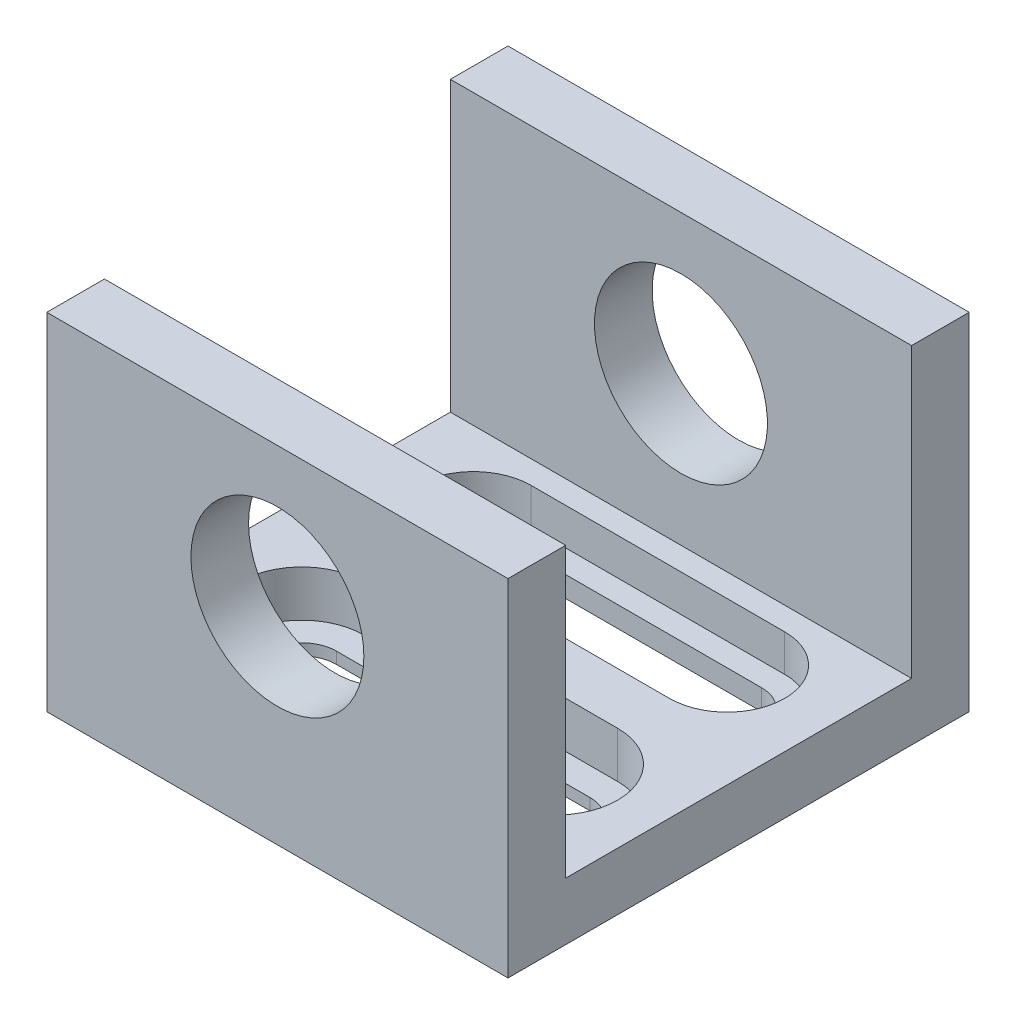
SolidWorks part; units mm, degrees
ref_plane "Front Plane" through (0, 0, 0) normal (0, 0, 1) x (1, 0, 0)
ref_plane "Top Plane" through (0, 0, 0) normal (0, 1, 0) x (1, 0, 0)
ref_plane "Right Plane" through (0, 0, 0) normal (1, 0, 0) x (0, 0, -1)
sketch "Sketch1" plane through (-35.1459, 0, 0) normal (1, 0, 0) x (0, 0, -1)
  line L1 (0, 0) -> (-19.05, 0)
  line L3 (0, 3.175) -> (-19.05, 3.175)
  line L5 (3.175, 19.05) -> (0, 19.05)
  line L6 (3.175, 19.05) -> (3.175, 0)
  line L7 (3.175, 0) -> (0, 0)
  line L8 (0, 19.05) -> (0, 3.175)
  line L13 (-19.05, 0) -> (-22.225, 0)
  line L14 (-19.05, 3.175) -> (-19.05, 19.05)
  line L15 (-19.05, 19.05) -> (-22.225, 19.05)
  line L16 (-22.225, 0) -> (-22.225, 19.05)
  dimension "D2" = 3.175
  dimension "D3" = 3.175
  dimension "D4" = 19.05
  dimension "D5" = 19.05
extrude "Boss-Extrude2" add sketch "Sketch1" along normal blind 25.4
sketch "Sketch3" plane through (0, 0, -3.175) normal (0, 0, -1) x (-1, 0, 0)
  line L0 (9.7459, 0) -> (35.1459, 0) construction
  line L2 (35.1459, 0) -> (35.1459, 19.05) construction
  circle A0 centre (22.4459, 11.3665) radius 4.7625
  dimension "D1" = 11.3665
  dimension "D2" = 12.7
extrude "Cut-Extrude1" cut sketch "Sketch3" against normal blind 36.576
sketch "Sketch4" plane through (0, 3.175, 0) normal (0, 1, 0) x (1, 0, 0)
  line L1 (-29.4309, -1.27) -> (-15.4609, -1.27)
  line L3 (-29.4309, -2.54) -> (-15.4609, -2.54)
  line L5 (-29.4309, -6.35) -> (-15.4609, -6.35)
  line L7 (-29.4309, -7.62) -> (-15.4609, -7.62)
  line L9 (-9.7459, -19.05) -> (-35.1459, -19.05) construction
  line L10 (-29.4309, -1.27) -> (-15.4609, -1.27)
  line L11 (-15.4609, -7.62) -> (-29.4309, -7.62)
  arc A0 (-29.4309, -2.54) -> (-29.4309, -6.35) centre (-29.4309, -4.445) ccw
  arc A1 (-29.4309, -1.27) -> (-29.4309, -7.62) centre (-29.4309, -4.445) ccw
  arc A2 (-15.4609, -2.54) -> (-15.4609, -6.35) centre (-15.4609, -4.445) cw
  arc A3 (-15.4609, -1.27) -> (-15.4609, -7.62) centre (-15.4609, -4.445) cw
  arc A4 (-29.4309, -1.27) -> (-29.4309, -7.62) centre (-29.4309, -4.445) ccw
  arc A5 (-15.4609, -1.27) -> (-15.4609, -7.62) centre (-15.4609, -4.445) cw
  dimension "D1" = 1.27
  dimension "D4" = 1.27
  dimension "D5" = 3.81
  dimension "D6" = 12.7
extrude "Cut-Extrude2" cut sketch "Sketch4" against normal blind 66.04 contours L3 A2 L5 A0
sketch "Sketch7" plane through (0, 3.175, 0) normal (0, 1, 0) x (1, 0, 0)
  line L1 (-29.4309, -2.54) -> (-15.4609, -2.54)
  line L3 (-29.4309, -1.27) -> (-15.4609, -1.27)
  line L5 (-29.4309, -6.35) -> (-15.4609, -6.35)
  line L7 (-29.4309, -7.62) -> (-15.4609, -7.62)
  arc A0 (-29.4309, -1.27) -> (-29.4309, -7.62) centre (-29.4309, -4.445) ccw
  arc A1 (-15.4609, -1.27) -> (-15.4609, -7.62) centre (-15.4609, -4.445) cw
  dimension "D1" = 1.27
  dimension "D2" = 13.97
  dimension "D3" = 1.27
  dimension "D4" = 13.97
extrude "Cut-Extrude3" cut sketch "Sketch7" against normal blind 2.032 contours L3 A1 L7 A0
sketch "Sketch8" plane through (0, 3.175, 0) normal (0, 1, 0) x (1, 0, 0)
  line L1 (-29.4309, -11.9938) -> (-15.4609, -11.9938)
  line L3 (-29.4309, -15.8038) -> (-15.4609, -15.8038)
  line L5 (-29.4309, -10.4698) -> (-15.4609, -10.4698)
  line L6 (-15.4609, -17.3278) -> (-29.4309, -17.3278)
  arc A0 (-15.4609, -15.8038) -> (-15.4609, -11.9938) centre (-15.4609, -13.8988) ccw
  arc A1 (-29.4309, -11.9938) -> (-29.4309, -15.8038) centre (-29.4309, -13.8988) ccw
  arc A3 (-29.4309, -10.4698) -> (-29.4309, -17.3278) centre (-29.4309, -13.8988) ccw
  arc A5 (-15.4609, -17.3278) -> (-15.4609, -10.4698) centre (-15.4609, -13.8988) ccw
  dimension "D1" = 3.81
extrude "Cut-Extrude4" cut sketch "Sketch8" against normal blind 2.54 contours L1 A1 L3 A0 | L6 A5 L5 A3 A1 L1 A0 L3 region at (-22.4459, 3.175, 13.8988) region at (-22.4459, 3.175, 10.6891)
extrude "Cut-Extrude5" cut sketch "Sketch8<3>" against normal through all contours L1 A1 L3 A0 region at (-22.4459, 3.175, 13.8988)
sketch "Sketch8<3>" plane through (0, 3.175, 0) normal (0, 1, 0) x (1, 0, 0) same geometry as "Sketch8"
